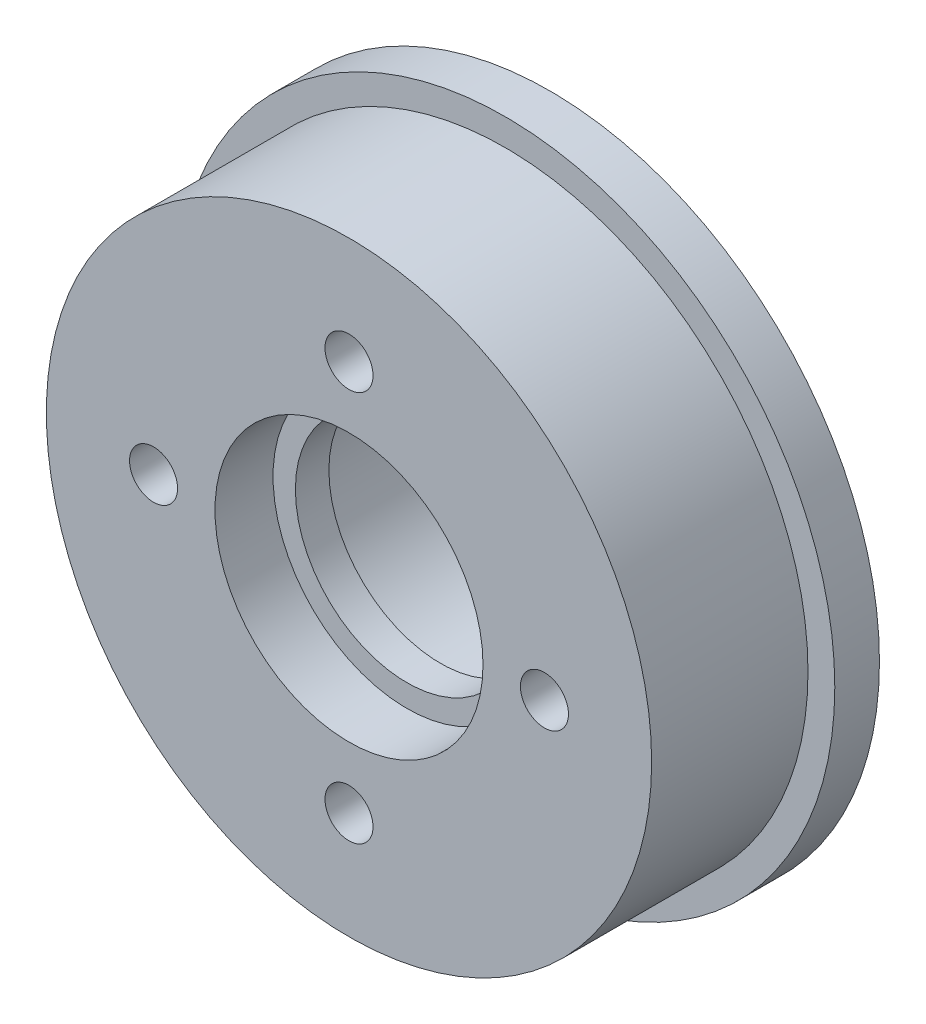
SolidWorks part; units mm, degrees
ref_plane "Front Plane" through (0, 0, 0) normal (0, 0, 1) x (1, 0, 0)
ref_plane "Top Plane" through (0, 0, 0) normal (0, 1, 0) x (1, 0, 0)
ref_plane "Right Plane" through (0, 0, 0) normal (1, 0, 0) x (0, 0, -1)
sketch "Sketch1" plane through (0, 0, 0) normal (0, 0, 1) x (1, 0, 0)
  circle A0 centre (0, 0) radius 29.5
  circle A1 centre (0, 0) radius 27.1
  circle A2 centre (0, 0) radius 12
  circle A3 centre (0, 0) radius 10
  dimension "D1" = 59
  dimension "D2" = 54.2
  dimension "D3" = 24
  dimension "D4" = 20
extrude "Boss-Extrude1" add sketch "Sketch1" along normal blind 4 contours A0 A1 region at (-28.6656, 0, 0)
extrude "Boss-Extrude2" add sketch "Sketch1<3>" along normal blind 18 contours A1 A2 region at (-26.3335, 0, 0)
sketch "Sketch1<3>" plane through (0, 0, 0) normal (0, 0, 1) x (1, 0, 0) same geometry as "Sketch1"
extrude "Boss-Extrude3" add sketch "Sketch1<4>" along normal blind 3 from offset 9.8 contours A2 A3 region at (-11.6606, 0, 0)
sketch "Sketch1<4>" plane through (0, 0, 0) normal (0, 0, 1) x (1, 0, 0) same geometry as "Sketch1"
sketch "Sketch2" plane through (0, 0, 0) normal (0, 0, 1) x (1, 0, 0)
  line L0 (-20, 15) -> (20, 15) construction
  line L1 (-20, -23) -> (20, -23) construction
  line L2 (-20, 18) -> (20, 18)
  line L3 (-16, -35) -> (16, -35)
  line L4 (-23, 15) -> (-23, -23)
  line L5 (23, 15) -> (23, -23)
  line L6 (-27.3518, -23) -> (-27.3518, -29) construction
  line L7 (-27.3518, -29) -> (-27.3518, -35) construction
  line L8 (-27.3518, -29) -> (32.2638, -29) construction
  line L9 (-27.3518, -35) -> (32.2638, -35) construction
  line L10 (-16, -35) -> (-16, -29)
  line L11 (16, -35) -> (16, -29)
  line L12 (-20.8734, -26.0636) -> (-17.0471, -27.4916)
  line L13 (0, 21.7483) -> (0, -55.2269) construction
  line L15 (20.8734, -26.0636) -> (17.0471, -27.4916)
  circle A0 centre (0, 0) radius 3.2
  circle A1 centre (20, 15) radius 1.25
  circle A2 centre (-20, 15) radius 1.25
  circle A3 centre (-20, -23) radius 1.25
  circle A4 centre (20, -23) radius 1.25
  arc A5 (-20, 18) -> (-23, 15) centre (-20, 15) ccw
  arc A6 (23, 15) -> (20, 18) centre (20, 15) ccw
  arc A8 (-16, -29) -> (-17.0471, -27.4916) centre (-17.61, -29) ccw
  arc A9 (16, -29) -> (17.0471, -27.4916) centre (17.61, -29) cw
  arc A11 (-23, -23) -> (-20.8734, -26.0636) centre (-19.73, -23) ccw
  arc A12 (23, -23) -> (20.8734, -26.0636) centre (19.73, -23) cw
  point P5 (0, 15)
  point P10 (0, -23)
  point P18 (0, -35)
  dimension "D1" = 15
  dimension "D3" = 2.5
  dimension "D4" = 2.5
  dimension "D7" = 2.5
  dimension "D8" = 2.5
  dimension "D11" = 6
  dimension "D9" = 6
  dimension "D12" = 6.4
  dimension "D15" = 3.27
  dimension "D16" = 1.61
  dimension "D2" = 40
  dimension "D5" = 40
  dimension "D6" = 23
  dimension "D10" = 32
  dimension "D13" = 6
  dimension "D14" = 6
  dimension "D17" = 7.3518
sketch "Sketch4" plane through (0, 0, 18) normal (0, 0, 1) x (1, 0, 0)
  circle A0 centre (0, 0) radius 17.5 construction
  circle A1 centre (0, 17.5) radius 2.15
  circle A2 centre (17.5, 0) radius 2.15
  circle A3 centre (0, -17.5) radius 2.15
  circle A4 centre (-17.5, 0) radius 2.15
  point P5 (-20.954, -1.5272)
  point P6 (0, 0)
  point P14 (0, 0)
  dimension "D1" = 35
  dimension "D2" = 4.3
  dimension "D3" = 4
extrude "Cut-Extrude1" cut sketch "Sketch4" against normal blind 6
